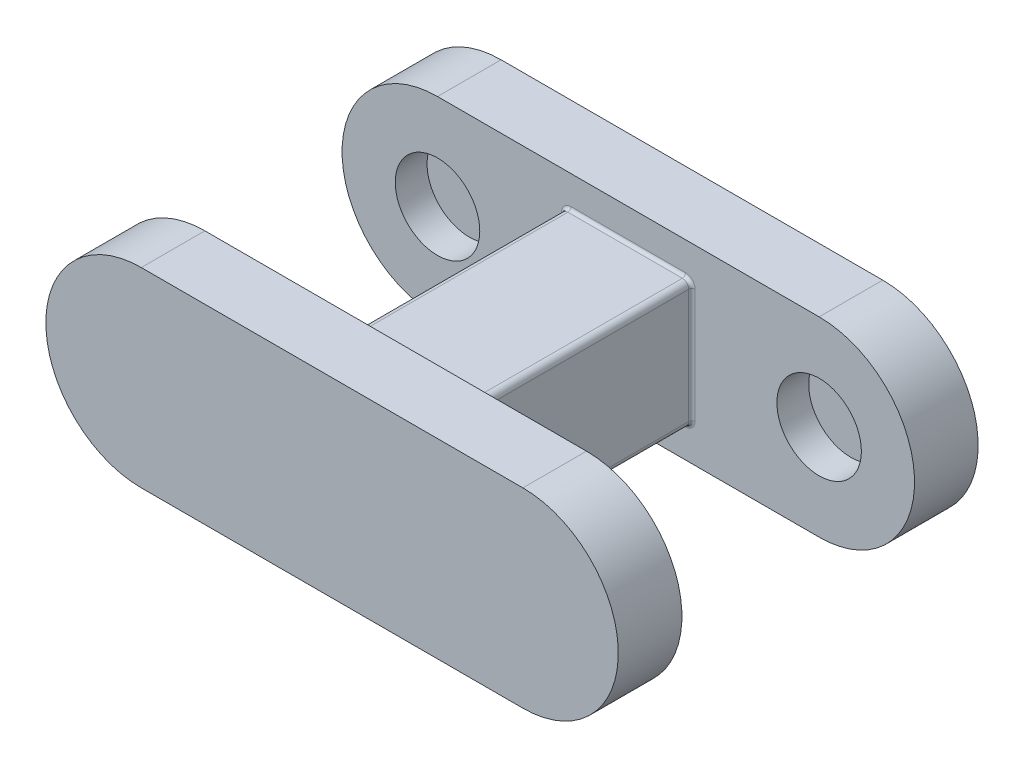
SolidWorks part; units mm, degrees
material "Hexcel AS4C (3000 Filaments)"
ref_plane "Front Plane" through (0, 0, 0) normal (0, 0, 1) x (1, 0, 0)
ref_plane "Top Plane" through (0, 0, 0) normal (0, 1, 0) x (1, 0, 0)
ref_plane "Right Plane" through (0, 0, 0) normal (1, 0, 0) x (0, 0, -1)
sketch "Sketch1" plane through (0, 0, 0) normal (0, 0, 1) x (1, 0, 0)
  line L0 (-76.2, 0) -> (76.2, 0) construction
  line L1 (-76.2, 38.1) -> (76.2, 38.1)
  line L2 (-76.2, -38.1) -> (76.2, -38.1)
  arc A0 (-76.2, 38.1) -> (-76.2, -38.1) centre (-76.2, 0) ccw
  arc A1 (76.2, -38.1) -> (76.2, 38.1) centre (76.2, 0) ccw
  point P2 (0, 0)
  point P7 (76.2, 0)
  point P8 (-76.2, 0)
  dimension "D1" = 38.1
extrude "Boss-Extrude1" add sketch "Sketch1" along normal blind 25.4
sketch "Sketch4" plane through (0, 0, 25.4) normal (0, 0, 1) x (1, 0, 0)
  circle A0 centre (76.2, 0) radius 16.875
  circle A1 centre (-76.2, 0) radius 16.875
  dimension "D1" = 33.75
  dimension "D2" = 33.75
extrude "Cut-Extrude1" cut sketch "Sketch4" against normal blind 12.7
sketch "Sketch5" plane through (0, 0, 25.4) normal (0, 0, 1) x (1, 0, 0)
  line L0 (-76.2, -38.1) -> (76.2, -38.1) construction
  line L1 (-25.4, 25.4) -> (25.4, 25.4)
  line L2 (-25.4, 25.4) -> (-25.4, -25.4)
  line L3 (-25.4, -25.4) -> (25.4, -25.4)
  line L4 (25.4, 25.4) -> (25.4, -25.4)
  line L5 (-25.4, 25.4) -> (25.4, -25.4) construction
  line L6 (-25.4, -25.4) -> (25.4, 25.4) construction
  circle A0 centre (-76.2, 0) radius 16.875 construction
  point P0 (0, 0)
  dimension "D1" = 12.7
  dimension "D2" = 50.8
extrude "Boss-Extrude2" add sketch "Sketch5" along normal blind 92.9
ref_plane "Plane4" through (0, 0, 71.85) normal (0, 0, 1) x (1, 0, 0)
mirror "Mirror2" about plane through (0, 0, 71.85) normal (0, 0, 1) of "Cut-Extrude1", "Boss-Extrude1"
fillet "Fillet1" radius 2.54 4 edges at (25.4, 25.4, 71.85) (25.4, -25.4, 71.85) (-25.4, -25.4, 71.85) (-25.4, 25.4, 71.85)
fillet "Fillet2" radius 1.27 8 edges at (-24.6561, 24.6561, 25.4) (0, 25.4, 25.4) (24.6561, 24.6561, 25.4) (25.4, 0, 25.4) (24.6561, -24.6561, 25.4) (0, -25.4, 25.4) (-24.6561, -24.6561, 25.4) (-25.4, 0, 25.4)
fillet "Fillet3" radius 1.27 8 edges at (-24.6561, 24.6561, 118.3) (0, 25.4, 118.3) (24.6561, 24.6561, 118.3) (25.4, 0, 118.3) (24.6561, -24.6561, 118.3) (0, -25.4, 118.3) (-24.6561, -24.6561, 118.3) (-25.4, 0, 118.3)
equation "\"D2@Sketch4\"=\"D1@Sketch4\""
